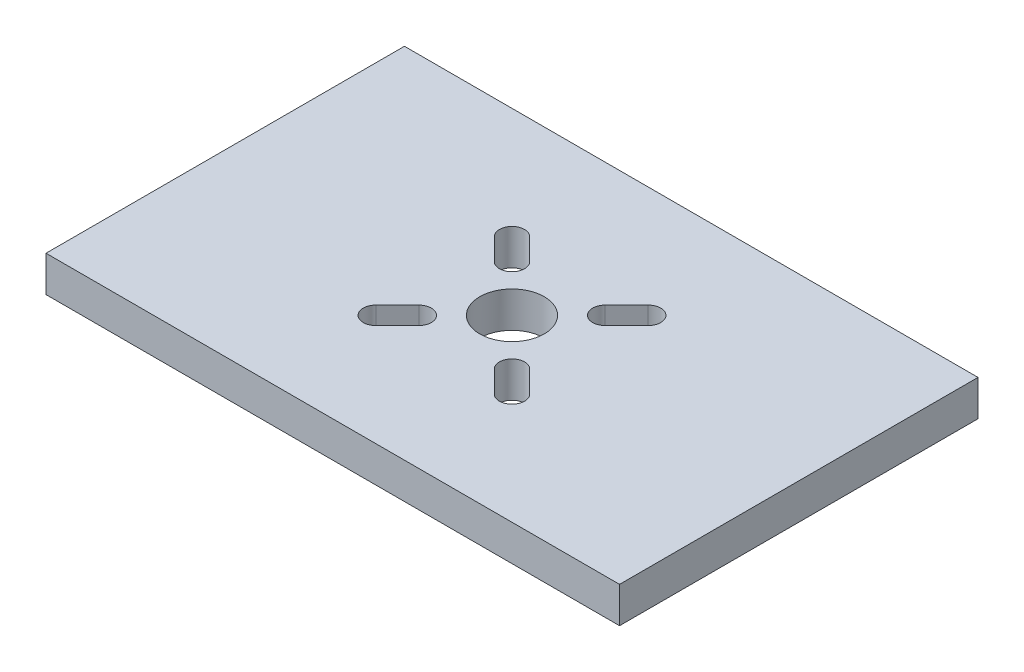
SolidWorks part; units mm, degrees
ref_plane "Front Plane" through (0, 0, 0) normal (0, 0, 1) x (1, 0, 0)
ref_plane "Top Plane" through (0, 0, 0) normal (0, 1, 0) x (1, 0, 0)
ref_plane "Right Plane" through (0, 0, 0) normal (1, 0, 0) x (0, 0, -1)
sketch "Sketch1" plane through (0, 0, 0) normal (0, 1, 0) x (1, 0, 0)
  line L1 (80, 50) -> (-80, 50)
  line L2 (80, 50) -> (80, -50)
  line L3 (80, -50) -> (-80, -50)
  line L4 (-80, 50) -> (-80, -50)
  line L5 (80, 50) -> (-80, -50) construction
  line L6 (80, -50) -> (-80, 50) construction
  point P0 (0, 0)
  dimension "D1" = 160
  dimension "D2" = 100
extrude "base" add sketch "Sketch1" along normal blind 10 contours L1 L4 L3 L2
sketch "Sketch2" plane through (0, 10, 0) normal (0, 1, 0) x (1, 0, 0)
  circle A0 centre (0, 0) radius 9
  dimension "D1" = 18
extrude "actuator cut" cut sketch "Sketch2" against normal blind 40
sketch "Sketch3" plane through (0, 10, 0) normal (0, 1, 0) x (1, 0, 0)
  line L0 (19, -19) -> (13, -13) construction
  line L1 (0, 0) -> (0, 19) construction
  line L2 (-19, -19) -> (19, 19) construction
  line L3 (-19, -19) -> (-13, -13) construction
  line L4 (-21.4749, -16.5251) -> (-15.4749, -10.5251)
  line L5 (-16.5251, -21.4749) -> (-10.5251, -15.4749)
  line L6 (21.4749, -16.5251) -> (15.4749, -10.5251)
  line L7 (16.5251, -21.4749) -> (10.5251, -15.4749)
  line L8 (0, 0) -> (19, 0) construction
  line L9 (19, 19) -> (13, 13) construction
  line L10 (21.4749, 16.5251) -> (15.4749, 10.5251)
  line L11 (16.5251, 21.4749) -> (10.5251, 15.4749)
  line L12 (-19, 19) -> (-13, 13) construction
  line L13 (-21.4749, 16.5251) -> (-15.4749, 10.5251)
  line L14 (-16.5251, 21.4749) -> (-10.5251, 15.4749)
  arc A4 (-21.4749, -16.5251) -> (-16.5251, -21.4749) centre (-19, -19) ccw
  arc A5 (-10.5251, -15.4749) -> (-15.4749, -10.5251) centre (-13, -13) ccw
  arc A6 (21.4749, -16.5251) -> (16.5251, -21.4749) centre (19, -19) cw
  arc A7 (10.5251, -15.4749) -> (15.4749, -10.5251) centre (13, -13) cw
  arc A8 (21.4749, 16.5251) -> (16.5251, 21.4749) centre (19, 19) ccw
  arc A9 (10.5251, 15.4749) -> (15.4749, 10.5251) centre (13, 13) ccw
  arc A10 (-21.4749, 16.5251) -> (-16.5251, 21.4749) centre (-19, 19) cw
  arc A11 (-10.5251, 15.4749) -> (-15.4749, 10.5251) centre (-13, 13) cw
  point P1 (-16, -16)
  point P10 (16, -16)
  point P20 (16, 16)
  point P27 (-16, 16)
  dimension "D5" = 3.5
  dimension "D4" = 19
  dimension "D1" = 13
  dimension "D2" = 19
  dimension "D3" = 45
  dimension "D6" = 19
extrude "Cut-Extrude1" cut sketch "Sketch3" against normal up to next
sketch "Sketch4" plane through (0, 0, 0) normal (0, -1, 0) x (1, 0, 0)
  line L0 (21.4749, 16.5251) -> (15.4749, 10.5251) construction
  line L1 (10.5251, 15.4749) -> (16.5251, 21.4749) construction
  line L2 (-15.4749, 10.5251) -> (-21.4749, 16.5251) construction
  line L3 (-16.5251, 21.4749) -> (-10.5251, 15.4749) construction
  line L4 (-10.5251, -15.4749) -> (-16.5251, -21.4749) construction
  line L5 (-21.4749, -16.5251) -> (-15.4749, -10.5251) construction
  line L6 (16.5251, -21.4749) -> (10.5251, -15.4749) construction
  line L7 (15.4749, -10.5251) -> (21.4749, -16.5251) construction
  line L8 (21.4749, 16.5251) -> (15.4749, 10.5251) construction
  line L9 (10.5251, 15.4749) -> (16.5251, 21.4749) construction
  line L10 (-15.4749, 10.5251) -> (-21.4749, 16.5251) construction
  line L11 (-16.5251, 21.4749) -> (-10.5251, 15.4749) construction
  line L12 (-10.5251, -15.4749) -> (-16.5251, -21.4749) construction
  line L13 (-21.4749, -16.5251) -> (-15.4749, -10.5251) construction
  line L14 (16.5251, -21.4749) -> (10.5251, -15.4749) construction
  line L15 (15.4749, -10.5251) -> (21.4749, -16.5251) construction
  line L16 (23.2426, 14.7574) -> (17.2426, 8.7574)
  line L17 (8.7574, 17.2426) -> (14.7574, 23.2426)
  line L18 (-17.2426, 8.7574) -> (-23.2426, 14.7574)
  line L19 (-14.7574, 23.2426) -> (-8.7574, 17.2426)
  line L20 (-8.7574, -17.2426) -> (-14.7574, -23.2426)
  line L21 (-23.2426, -14.7574) -> (-17.2426, -8.7574)
  line L22 (14.7574, -23.2426) -> (8.7574, -17.2426)
  line L23 (17.2426, -8.7574) -> (23.2426, -14.7574)
  arc A0 (10.5251, 15.4749) -> (15.4749, 10.5251) centre (13, 13) ccw construction
  arc A1 (21.4749, 16.5251) -> (16.5251, 21.4749) centre (19, 19) ccw construction
  arc A2 (-16.5251, 21.4749) -> (-21.4749, 16.5251) centre (-19, 19) ccw construction
  arc A3 (-15.4749, 10.5251) -> (-10.5251, 15.4749) centre (-13, 13) ccw construction
  arc A4 (-21.4749, -16.5251) -> (-16.5251, -21.4749) centre (-19, -19) ccw construction
  arc A5 (-10.5251, -15.4749) -> (-15.4749, -10.5251) centre (-13, -13) ccw construction
  arc A6 (15.4749, -10.5251) -> (10.5251, -15.4749) centre (13, -13) ccw construction
  arc A7 (16.5251, -21.4749) -> (21.4749, -16.5251) centre (19, -19) ccw construction
  arc A8 (10.5251, 15.4749) -> (15.4749, 10.5251) centre (13, 13) ccw construction
  arc A9 (21.4749, 16.5251) -> (16.5251, 21.4749) centre (19, 19) ccw construction
  arc A10 (-16.5251, 21.4749) -> (-21.4749, 16.5251) centre (-19, 19) ccw construction
  arc A11 (-15.4749, 10.5251) -> (-10.5251, 15.4749) centre (-13, 13) ccw construction
  arc A12 (-21.4749, -16.5251) -> (-16.5251, -21.4749) centre (-19, -19) ccw construction
  arc A13 (-10.5251, -15.4749) -> (-15.4749, -10.5251) centre (-13, -13) ccw construction
  arc A14 (15.4749, -10.5251) -> (10.5251, -15.4749) centre (13, -13) ccw construction
  arc A15 (16.5251, -21.4749) -> (21.4749, -16.5251) centre (19, -19) ccw construction
  arc A16 (8.7574, 17.2426) -> (17.2426, 8.7574) centre (13, 13) ccw
  arc A17 (23.2426, 14.7574) -> (14.7574, 23.2426) centre (19, 19) ccw
  arc A18 (-14.7574, 23.2426) -> (-23.2426, 14.7574) centre (-19, 19) ccw
  arc A19 (-17.2426, 8.7574) -> (-8.7574, 17.2426) centre (-13, 13) ccw
  arc A20 (-23.2426, -14.7574) -> (-14.7574, -23.2426) centre (-19, -19) ccw
  arc A21 (-8.7574, -17.2426) -> (-17.2426, -8.7574) centre (-13, -13) ccw
  arc A22 (17.2426, -8.7574) -> (8.7574, -17.2426) centre (13, -13) ccw
  arc A23 (14.7574, -23.2426) -> (23.2426, -14.7574) centre (19, -19) ccw
  dimension "D1" = 2.5
split line "Split Line1"
equation "\"D4@Sketch3\"=\"D2@Sketch3\""
equation "\"D6@Sketch3\"=\"D2@Sketch3\""
